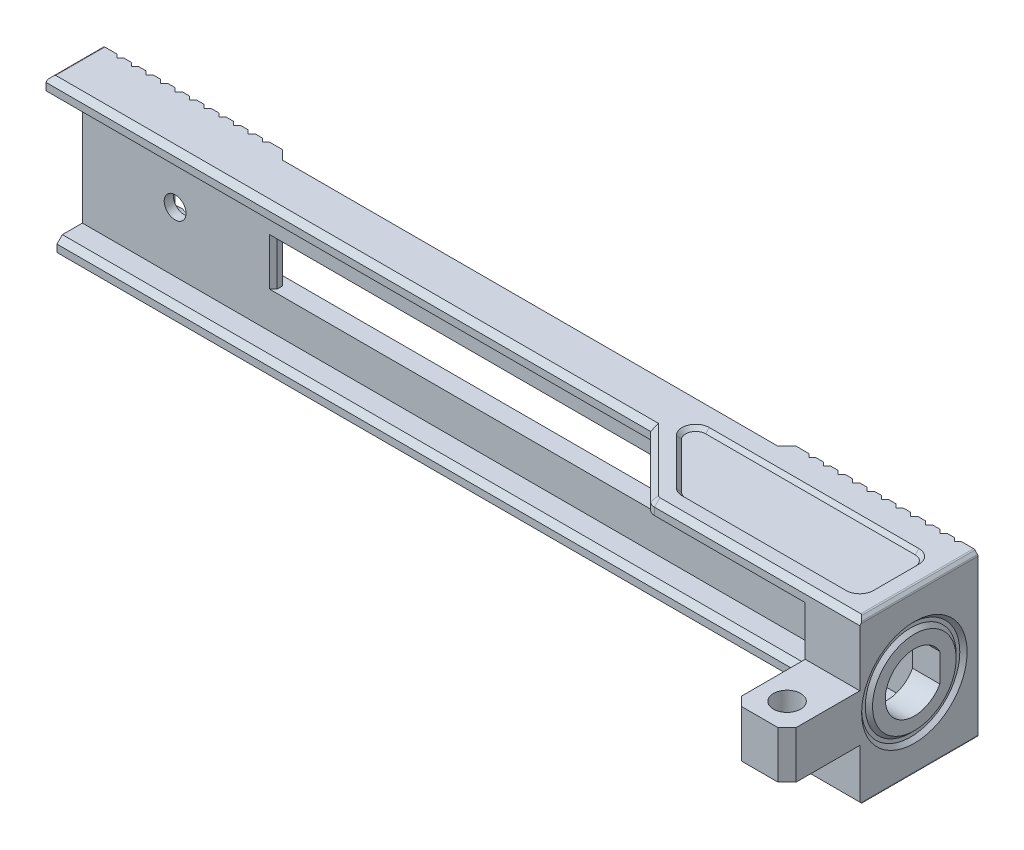
SolidWorks part; units mm, degrees
ref_plane "前视基准面" through (0, 0, 0) normal (0, 0, 1) x (1, 0, 0)
ref_plane "上视基准面" through (0, 0, 0) normal (0, 1, 0) x (1, 0, 0)
ref_plane "右视基准面" through (0, 0, 0) normal (1, 0, 0) x (0, 0, -1)
sketch "草图1" plane through (0, 0, 0) normal (0, 1, 0) x (1, 0, 0)
  line L0 (76.5, 6) -> (96.5, 6)
  line L1 (0, 0) -> (66.5, 0)
  line L2 (0, 0) -> (0, 6)
  line L3 (0, 6) -> (20, 6)
  line L4 (96.5, -7) -> (96.5, 6)
  line L7 (21, 5) -> (75.5, 5)
  line L9 (20, 6) -> (21, 5)
  line L10 (76.5, 6) -> (75.5, 5)
  line L11 (66.5, 0) -> (73.5, -7)
  line L14 (96.5, -7) -> (73.5, -7)
  line L16 (20, 6) -> (76.5, 6) construction
  dimension "D1" = 6
  dimension "D2" = 96.5
  dimension "D3" = 20
  dimension "D4" = 20
  dimension "D5" = 1
  dimension "D6" = 45
  dimension "D7" = 45
  dimension "D8" = 13
  dimension "D9" = 45
  dimension "D10" = 30
extrude "凸台-拉伸1" add sketch "草图1" along normal blind 18
sketch "草图2" plane through (0, 0, 0) normal (-1, 0, 0) x (0, 0, 1)
  line L0 (-6, 18) -> (0, 18) construction
  line L1 (-4, 2) -> (7, 2)
  line L2 (-4, 2) -> (-4, 16)
  line L3 (-4, 16) -> (7, 16)
  line L4 (7, 2) -> (7, 16)
  line L5 (-6, 0) -> (0, 0) construction
  line L6 (-6, 18) -> (-6, 0) construction
  line L9 (7, 18) -> (7, 0) construction
  dimension "D1" = 2
  dimension "D2" = 2
  dimension "D3" = 2
  dimension "D4" = 0
extrude "切除-拉伸1" cut sketch "草图2" against normal offset from surface (93.5 mm away) 3 up to face at (96.5, 9, 0.5)
sketch "草图3" plane through (96.5, 0, 0) normal (1, 0, 0) x (0, 0, -1)
  line L2 (-18.4443, 9) -> (19.6472, 9) construction
  line L3 (-7, 18) -> (6, 18) construction
  line L4 (-7, 0) -> (6, 0) construction
  line L5 (6, 18) -> (6, 0) construction
  line L6 (1.8, 7.4508) -> (1.8, 10.5492)
  arc A0 (1.8, 10.5492) -> (1.8, 7.4508) centre (-1, 9) ccw
  dimension "D1" = 6.4
  dimension "D2" = 7
  dimension "D3" = 2.8
extrude "切除-拉伸2" cut sketch "草图3" against normal up to next
sketch "草图4" plane through (93.5, 0, 0) normal (-1, 0, 0) x (0, 0, 1)
  line L0 (7, 2) -> (-4, 2) construction
  line L1 (7, 16) -> (6, 16)
  line L2 (7, 16) -> (7, 2)
  line L3 (7, 2) -> (6, 2)
  line L4 (6, 16) -> (6, 2)
  dimension "D1" = 1
extrude "凸台-拉伸2" add sketch "草图4" along normal blind 3
sketch "草图5" plane through (96.5, 0, 0) normal (1, 0, 0) x (0, 0, -1)
  line L0 (-7, 18) -> (-7, 0) construction
  line L1 (-7, 11.2) -> (-15, 11.2)
  line L2 (-7, 11.2) -> (-7, 6)
  line L3 (-7, 6) -> (-15, 6)
  line L4 (-15, 11.2) -> (-15, 6)
  line L5 (-7, 18) -> (6, 18) construction
  dimension "D1" = 8
  dimension "D2" = 5.2
  dimension "D3" = 6.8
extrude "凸台-拉伸3" add sketch "草图5" against normal blind 6
sketch "草图6" plane through (96.5, 0, 0) normal (1, 0, 0) x (0, 0, -1)
  circle A0 centre (-1, 9) radius 5
  circle A1 centre (-1, 9) radius 5.4
  dimension "D1" = 10
  dimension "D2" = 10.8
extrude "切除-拉伸3" cut sketch "草图6" against normal blind 0.4
chamfer "倒角2" distance 0.4 angle 45 2 edges at (96.5, 9, -4) (96.5, 9, -4.4)
sketch "草图7" plane through (0, 0, 0) normal (-1, 0, 0) x (0, 0, 1)
  line L0 (-6, 0) -> (0, 0) construction
  line L1 (-1.2, 0) -> (18.8, 0)
  line L2 (-1.2, 0) -> (-1.2, 2)
  line L3 (-1.2, 2) -> (18.8, 2)
  line L4 (18.8, 0) -> (18.8, 2)
  line L6 (-4, 2) -> (0, 2) construction
  line L7 (0, 2) -> (0, 0) construction
  dimension "D1" = 1.2
  dimension "D2" = 20
extrude "切除-拉伸4" cut sketch "草图7" against normal blind 86
sketch "草图8" plane through (0, 11.2, 0) normal (0, 1, 0) x (1, 0, 0)
  line L0 (93.5, -9.3814) -> (93.5, -17.2025) construction
  line L1 (90.5, -7) -> (90.5, -15) construction
  line L2 (96.5, -7) -> (96.5, -15) construction
  line L3 (90.5, -15) -> (96.5, -15) construction
  circle A0 centre (93.5, -12) radius 1.5
  dimension "D1" = 3
  dimension "D2" = 3
extrude "切除-拉伸5" cut sketch "草图8" against normal through all
chamfer "倒角3" distance 1 angle 45 2 edges at (90.5, 8.6, 15) (96.5, 8.6, 15)
sketch "草图9" plane through (0, 0, -6) normal (0, 0, -1) x (-1, 0, 0)
  line L1 (-75.5, 11.2) -> (-21, 11.2)
  line L2 (-75.5, 11.2) -> (-75.5, 6)
  line L3 (-75.5, 6) -> (-21, 6)
  line L4 (-21, 11.2) -> (-21, 6)
  line L10 (-96.5, 18) -> (-96.5, 0) construction
  line L11 (0, 18) -> (0, 0) construction
  line L12 (-75.5, 0) -> (-21, 0) construction
  dimension "D1" = 5.2
  dimension "D2" = 21
  dimension "D3" = 21
  dimension "D4" = 6
extrude "切除-拉伸6" cut sketch "草图9" against normal up to next
sketch "草图10" plane through (0, 0, -5) normal (0, 0, -1) x (-1, 0, 0)
  line L0 (-76.5, 18) -> (-76.5, 0) construction
  line L1 (-76.5, 11.2) -> (-20, 11.2)
  line L2 (-76.5, 11.2) -> (-76.5, 12.2)
  line L3 (-76.5, 12.2) -> (-61.5, 12.2)
  line L4 (-20, 11.2) -> (-20, 12.2)
  line L5 (-20, 18) -> (-20, 0) construction
  line L6 (-75.5, 18) -> (-21, 18) construction
  line L7 (-76.5, 6) -> (-20, 6)
  line L8 (-76.5, 6) -> (-76.5, 5)
  line L9 (-76.5, 5) -> (-61.5, 5)
  line L10 (-20, 6) -> (-20, 5)
  line L12 (-61.5, 12.2) -> (-61.5, 18)
  line L13 (-61.5, 18) -> (-60.5, 18)
  line L14 (-60.5, 12.2) -> (-60.5, 18)
  line L15 (-75.5, 0) -> (-21, 0) construction
  line L17 (-36, 12.2) -> (-36, 18)
  line L18 (-36, 18) -> (-35, 18)
  line L19 (-35, 12.2) -> (-35, 18)
  line L21 (-61.5, 5) -> (-61.5, 0)
  line L22 (-61.5, 0) -> (-60.5, 0)
  line L23 (-60.5, 5) -> (-60.5, 0)
  line L24 (-75.5, 6) -> (-21, 6) construction
  line L26 (-36, 5) -> (-36, 0)
  line L27 (-36, 0) -> (-35, 0)
  line L28 (-35, 5) -> (-35, 0)
  line L29 (-21, 11.2) -> (-75.5, 11.2) construction
  line L30 (-60.5, 5) -> (-36, 5)
  line L31 (-60.5, 12.2) -> (-36, 12.2)
  line L32 (-35, 12.2) -> (-20, 12.2)
  line L33 (-35, 5) -> (-20, 5)
  dimension "D1" = 1
  dimension "D2" = 1
  dimension "D3" = 1
  dimension "D4" = 1
  dimension "D5" = 15
  dimension "D6" = 15
extrude "凸台-拉伸4" add sketch "草图10" along normal blind 1
chamfer "倒角5" distance 1 angle 45 6 edges at (68.5, 5, -5) (28, 5, -5) (48.25, 5, -5) (28, 12.2, -5) (48.25, 12.2, -5) (68.5, 12.2, -5)
chamfer "倒角6" distance 1 angle 75 4 edges at (61, 18, -6) (35.5, 18, -6) (35.5, 0, -6) (61, 0, -6) first distance on face at (50.6667, 18, -3.5556) first distance on face at (52.4444, 0, -3.6889)
fillet "圆角3" radius 5 4 edges at (35.5, 14.2679, -6) (35.5, 3.7321, -6) (61, 3.7321, -6) (61, 14.2679, -6)
sketch "草图13" plane through (0, 0, -6) normal (0, 0, -1) x (-1, 0, 0)
  line L2 (-28.2556, 8.6) -> (3.7512, 8.6) construction
  line L3 (-76.5, 11.2) -> (-20, 11.2) construction
  line L4 (-20, 6) -> (-76.5, 6) construction
  line L5 (0, 18) -> (0, 0) construction
  circle A0 centre (-10.2, 8.6) radius 2.1
  dimension "D1" = 10.2
  dimension "D2" = 4.2
extrude "切除-拉伸9" cut sketch "草图13" against normal blind 1
sketch "草图14" plane through (0, 0, -5) normal (0, 0, -1) x (-1, 0, 0)
  circle A0 centre (-10.2, 8.6) radius 1.2
  dimension "D1" = 2.4
extrude "切除-拉伸10" cut sketch "草图14" against normal up to next
sketch "草图11" plane through (0, 18, 0) normal (0, 1, 0) x (1, 0, 0)
  line L0 (66.3284, 3) -> (94.5, 3)
  line L1 (94.5, 3) -> (94.5, -5)
  line L2 (94.5, -5) -> (74.3284, -5)
  line L3 (74.3284, -5) -> (66.3284, 3)
  line L4 (66.5, 0) -> (73.5, -7) construction
  line L5 (73.5, -7) -> (96.5, -7) construction
  line L6 (96.5, -7) -> (96.5, 6) construction
  line L7 (75.5, 5) -> (61.5, 5) construction
  dimension "D1" = 2
  dimension "D2" = 2
  dimension "D3" = 2
  dimension "D4" = 2
extrude "切除-拉伸7" cut sketch "草图11" against normal blind 0.4
fillet "圆角4" radius 1 2 edges at (86, 1, 7) (73.5, 17, 7)
chamfer "倒角9" distance 0.6 angle 45 16 edges at (85.2071, 18, 7) (73.5315, 18, 6.9239) (69.8536, 18, 3.3536) (33.25, 18, 0) (91.75, 0, 7) (86.2929, 0, 6.7071) (86, 0, 2.4) (43, 0, -1.2) (88.75, 2, 7) (86.2929, 2, 6.7071) (86, 2, 2.4) (43, 2, -1.2) (82.2071, 16, 7) (73.5315, 16, 6.9239) (69.8536, 16, 3.3536) (33.25, 16, 0)
chamfer "倒角8" distance 0.4 angle 45 4 edges at (96.5, 0, 0.2) (96.5, 18, 0.2) (0, 0, -3.9) (0, 18, -3.3)
fillet "圆角2" radius 0.2 8 edges at (0.4, 18, -3.3) (0, 17.6, -3.1) (0, 0.4, -3.7) (0.4, 0, -3.9) (96.1, 0, 0.2) (96.5, 0.4, 0.4) (96.1, 18, 0.2) (96.5, 17.6, 0.4)
sketch "草图12" plane through (0, 18, 0) normal (0, 1, 0) x (1, 0, 0)
  line L0 (20, 6) -> (0.4828, 6) construction
  line L1 (1.8, 6) -> (2.6, 6)
  line L2 (1.8, 6) -> (1.8, 5.6) construction
  line L3 (1.8, 5.6) -> (2.6, 5.6) construction
  line L4 (2.6, 6) -> (2.6, 5.6) construction
  line L73 (3.4, 6) -> (4.2, 6)
  line L74 (0, 0.6) -> (0, 4) construction
  line L75 (1.8, 6) -> (2.2, 5.6)
  line L76 (2.2, 5.6) -> (2.6, 6)
  line L77 (3.4, 6) -> (3.8, 5.6)
  line L78 (3.8, 5.6) -> (4.2, 6)
  line L79 (5, 6) -> (5.8, 6)
  line L80 (5, 6) -> (5.4, 5.6)
  line L81 (5.4, 5.6) -> (5.8, 6)
  line L82 (6.6, 6) -> (7.4, 6)
  line L83 (6.6, 6) -> (7, 5.6)
  line L84 (7, 5.6) -> (7.4, 6)
  line L85 (8.2, 6) -> (9, 6)
  line L86 (8.2, 6) -> (8.6, 5.6)
  line L87 (8.6, 5.6) -> (9, 6)
  line L88 (9.8, 6) -> (10.6, 6)
  line L89 (9.8, 6) -> (10.2, 5.6)
  line L90 (10.2, 5.6) -> (10.6, 6)
  line L91 (11.4, 6) -> (12.2, 6)
  line L92 (11.4, 6) -> (11.8, 5.6)
  line L93 (11.8, 5.6) -> (12.2, 6)
  line L94 (13, 6) -> (13.8, 6)
  line L95 (13, 6) -> (13.4, 5.6)
  line L96 (13.4, 5.6) -> (13.8, 6)
  line L97 (14.6, 6) -> (15.4, 6)
  line L98 (14.6, 6) -> (15, 5.6)
  line L99 (15, 5.6) -> (15.4, 6)
  line L100 (16.2, 6) -> (17, 6)
  line L101 (16.2, 6) -> (16.6, 5.6)
  line L102 (16.6, 5.6) -> (17, 6)
  line L103 (17.8, 6) -> (18.6, 6)
  line L104 (17.8, 6) -> (18.2, 5.6)
  line L105 (18.2, 5.6) -> (18.6, 6)
  line L106 (1.8, 6) -> (3.4, 6) construction
  line L107 (96.0172, 6) -> (76.5, 6) construction
  line L108 (93.9, 6) -> (94.7, 6)
  line L109 (93.9, 6) -> (93.9, 5.6) construction
  line L110 (93.9, 5.6) -> (94.7, 5.6) construction
  line L111 (94.7, 6) -> (94.7, 5.6) construction
  line L112 (96.5, 6) -> (96.5, -6.8828) construction
  line L113 (93.9, 6) -> (94.3, 5.6)
  line L114 (94.3, 5.6) -> (94.7, 6)
  line L115 (92.3, 6) -> (92.7, 5.6)
  line L116 (92.3, 6) -> (93.1, 6)
  line L117 (92.7, 5.6) -> (93.1, 6)
  line L118 (90.7, 6) -> (91.1, 5.6)
  line L119 (90.7, 6) -> (91.5, 6)
  line L120 (91.1, 5.6) -> (91.5, 6)
  line L121 (89.1, 6) -> (89.5, 5.6)
  line L122 (89.1, 6) -> (89.9, 6)
  line L123 (89.5, 5.6) -> (89.9, 6)
  line L124 (87.5, 6) -> (87.9, 5.6)
  line L125 (87.5, 6) -> (88.3, 6)
  line L126 (87.9, 5.6) -> (88.3, 6)
  line L127 (85.9, 6) -> (86.3, 5.6)
  line L128 (85.9, 6) -> (86.7, 6)
  line L129 (86.3, 5.6) -> (86.7, 6)
  line L130 (84.3, 6) -> (84.7, 5.6)
  line L131 (84.3, 6) -> (85.1, 6)
  line L132 (84.7, 5.6) -> (85.1, 6)
  line L133 (82.7, 6) -> (83.1, 5.6)
  line L134 (82.7, 6) -> (83.5, 6)
  line L135 (83.1, 5.6) -> (83.5, 6)
  line L136 (81.1, 6) -> (81.5, 5.6)
  line L137 (81.1, 6) -> (81.9, 6)
  line L138 (81.5, 5.6) -> (81.9, 6)
  line L139 (79.5, 6) -> (79.9, 5.6)
  line L140 (79.5, 6) -> (80.3, 6)
  line L141 (79.9, 5.6) -> (80.3, 6)
  line L142 (77.9, 6) -> (78.3, 5.6)
  line L143 (77.9, 6) -> (78.7, 6)
  line L144 (78.3, 5.6) -> (78.7, 6)
  line L145 (93.9, 6) -> (92.3, 6) construction
  dimension "D1" = 0.8
  dimension "D2" = 0.4
  dimension "D4" = 1.6
  dimension "D5" = 1.8
  dimension "D6" = 0.8
  dimension "D7" = 0.4
  dimension "D8" = 1.8
  dimension "D9" = 11
  dimension "D10" = 1.6
  dimension "D3" = 11
extrude "切除-拉伸8" cut sketch "草图12" against normal through all
sketch "草图15" plane through (0, 0, 0) normal (0, -1, 0) x (1, 0, 0)
  line L0 (86, 7) -> (96.0172, 7) construction
  line L1 (88, 5) -> (94.5, 5)
  line L2 (88, 5) -> (88, -4)
  line L3 (88, -4) -> (94.5, -4)
  line L4 (94.5, 5) -> (94.5, -4)
  line L5 (86, -1.2) -> (86, 7) construction
  line L6 (96.5, 6.8828) -> (96.5, -6) construction
  line L7 (96.0172, -6) -> (94.7, -6) construction
  dimension "D1" = 2
  dimension "D2" = 2
  dimension "D3" = 2
  dimension "D4" = 2
extrude "切除-拉伸11" cut sketch "草图15" against normal blind 0.4
fillet "圆角1" radius 1.5 8 edges at (94.5, 17.8, 5) (94.5, 17.8, -3) (74.3284, 17.8, 5) (66.3284, 17.8, -3) (94.5, 0.2, -4) (88, 0.2, -4) (88, 0.2, 5) (94.5, 0.2, 5)
chamfer "倒角7" distance 0.4 angle 45 16 edges at (83.9749, 17.6, 5) (94.0607, 17.6, 4.5607) (74.3757, 17.6, 4.8858) (94.5, 17.6, 1) (71.3891, 17.6, 2.0607) (94.0607, 17.6, -2.5607) (68.5639, 17.6, -2.074) (81.4749, 17.6, -3) (88.4393, 0.4, -3.5607) (91.25, 0.4, -4) (88, 0.4, 0.5) (94.0607, 0.4, -3.5607) (88.4393, 0.4, 4.5607) (94.5, 0.4, 0.5) (91.25, 0.4, 5) (94.0607, 0.4, 4.5607)
chamfer "倒角10" distance 0.4 angle 45 2 edges at (75.5, 8.6, -4) (21, 8.6, -4)
